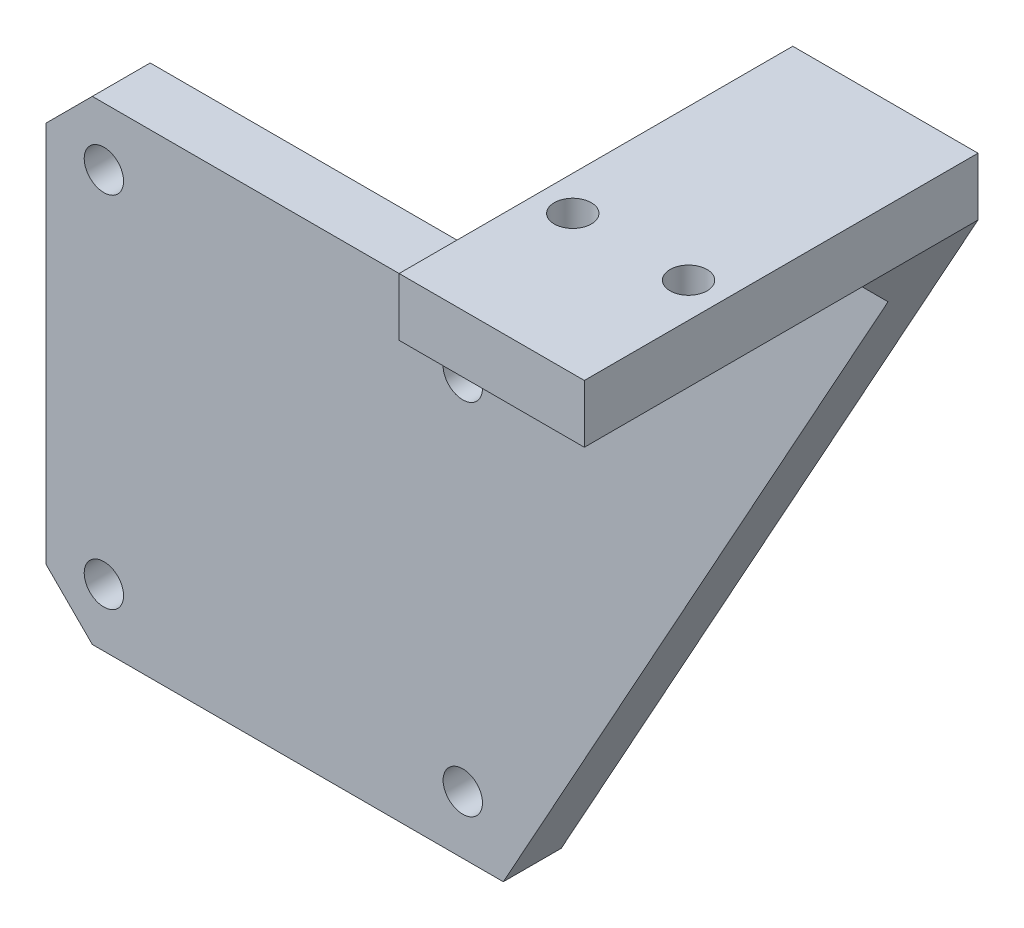
SolidWorks part; units mm, degrees
ref_plane "Přední rovina" through (0, 0, 0) normal (0, 0, 1) x (1, 0, 0)
ref_plane "Horní rovina" through (0, 0, 0) normal (0, 1, 0) x (1, 0, 0)
ref_plane "Pravá rovina" through (0, 0, 0) normal (1, 0, 0) x (0, 0, -1)
ref_plane "Rovina4" through (0, 0, 5) normal (0, 0, 1) x (1, 0, 0)
sketch "Skica1" plane through (0, 0, 5) normal (0, 0, 1) x (1, 0, 0)
  line L0 (46, 70) -> (-29.5, 70)
  line L1 (-29.5, 70) -> (-29.5, 0)
  line L2 (-29.5, 0) -> (10, 0)
  line L3 (10, 0) -> (46, 65)
  line L4 (46, 65) -> (46, 70)
extrude "Přidat vysunutím1" add sketch "Skica1" against normal blind 5
sketch "Skica2" plane through (0, 0, 5) normal (0, 0, 1) x (1, 0, 0)
  line L0 (25.8333, 60) -> (30, 65)
  line L1 (30, 65) -> (30, 70)
  line L2 (30, 70) -> (-29.5, 70)
  line L3 (-29.5, 70) -> (-29.5, 41)
  line L4 (-29.5, 41) -> (10, 41)
  line L5 (10, 41) -> (25.8333, 60)
extrude "Odebrat vysunutím1" cut sketch "Skica2" against normal through all
sketch "Skica3" plane through (0, 0, 5) normal (0, 0, 1) x (1, 0, 0)
  line L0 (30, 65) -> (30, 70)
  line L1 (30, 70) -> (46, 70)
  line L2 (46, 70) -> (46, 65)
  line L3 (46, 65) -> (30, 65)
extrude "Přidat vysunutím2" add sketch "Skica3" along normal blind 20
sketch "Skica5" plane through (0, 0, 5) normal (0, 0, 1) x (1, 0, 0)
  line L0 (-23.0975, 4.4681) -> (-23.0109, 4.8192)
  line L1 (-23.0109, 4.8192) -> (-23.0109, 5.1808)
  line L2 (-23.0109, 5.1808) -> (-23.0975, 5.5319)
  line L3 (-23.0975, 5.5319) -> (-23.2655, 5.8521)
  line L4 (-23.2655, 5.8521) -> (-23.5053, 6.1228)
  line L5 (-23.5053, 6.1228) -> (-23.8029, 6.3282)
  line L6 (-23.8029, 6.3282) -> (-24.141, 6.4564)
  line L7 (-24.141, 6.4564) -> (-24.5, 6.5)
  line L8 (-24.5, 6.5) -> (-24.859, 6.4564)
  line L9 (-24.859, 6.4564) -> (-25.1971, 6.3282)
  line L10 (-25.1971, 6.3282) -> (-25.4947, 6.1228)
  line L11 (-25.4947, 6.1228) -> (-25.7345, 5.8521)
  line L12 (-25.7345, 5.8521) -> (-25.9025, 5.5319)
  line L13 (-25.9025, 5.5319) -> (-25.9891, 5.1808)
  line L14 (-25.9891, 5.1808) -> (-25.9891, 4.8192)
  line L15 (-25.9891, 4.8192) -> (-25.9025, 4.4681)
  line L16 (-25.9025, 4.4681) -> (-25.7345, 4.1479)
  line L17 (-25.7345, 4.1479) -> (-25.4947, 3.8772)
  line L18 (-25.4947, 3.8772) -> (-25.1971, 3.6718)
  line L19 (-25.1971, 3.6718) -> (-24.859, 3.5436)
  line L20 (-24.859, 3.5436) -> (-24.5, 3.5)
  line L21 (-24.5, 3.5) -> (-24.141, 3.5436)
  line L22 (-24.141, 3.5436) -> (-23.8029, 3.6718)
  line L23 (-23.8029, 3.6718) -> (-23.5053, 3.8772)
  line L24 (-23.5053, 3.8772) -> (-23.2655, 4.1479)
  line L25 (-23.2655, 4.1479) -> (-23.0975, 4.4681)
extrude "Odebrat vysunutím3" cut sketch "Skica5" against normal through all
sketch "Skica6" plane through (0, 0, 5) normal (0, 0, 1) x (1, 0, 0)
  line L0 (5.5053, 3.8772) -> (5.8029, 3.6718)
  line L1 (5.8029, 3.6718) -> (6.141, 3.5436)
  line L2 (6.141, 3.5436) -> (6.5, 3.5)
  line L3 (6.5, 3.5) -> (6.859, 3.5436)
  line L4 (6.859, 3.5436) -> (7.1971, 3.6718)
  line L5 (7.1971, 3.6718) -> (7.4947, 3.8772)
  line L6 (7.4947, 3.8772) -> (7.7345, 4.1479)
  line L7 (7.7345, 4.1479) -> (7.9025, 4.4681)
  line L8 (7.9025, 4.4681) -> (7.9891, 4.8192)
  line L9 (7.9891, 4.8192) -> (7.9891, 5.1808)
  line L10 (7.9891, 5.1808) -> (7.9025, 5.5319)
  line L11 (7.9025, 5.5319) -> (7.7345, 5.8521)
  line L12 (7.7345, 5.8521) -> (7.4947, 6.1228)
  line L13 (7.4947, 6.1228) -> (7.1971, 6.3282)
  line L14 (7.1971, 6.3282) -> (6.859, 6.4564)
  line L15 (6.859, 6.4564) -> (6.5, 6.5)
  line L16 (6.5, 6.5) -> (6.141, 6.4564)
  line L17 (6.141, 6.4564) -> (5.8029, 6.3282)
  line L18 (5.8029, 6.3282) -> (5.5053, 6.1228)
  line L19 (5.5053, 6.1228) -> (5.2655, 5.8521)
  line L20 (5.2655, 5.8521) -> (5.0975, 5.5319)
  line L21 (5.0975, 5.5319) -> (5.0109, 5.1808)
  line L22 (5.0109, 5.1808) -> (5.0109, 4.8192)
  line L23 (5.0109, 4.8192) -> (5.0975, 4.4681)
  line L24 (5.0975, 4.4681) -> (5.2655, 4.1479)
  line L25 (5.2655, 4.1479) -> (5.5053, 3.8772)
extrude "Odebrat vysunutím4" cut sketch "Skica6" against normal through all
sketch "Skica7" plane through (0, 0, 5) normal (0, 0, 1) x (1, 0, 0)
  line L0 (-23.3772, 35.0053) -> (-23.1718, 35.3029)
  line L1 (-23.1718, 35.3029) -> (-23.0436, 35.641)
  line L2 (-23.0436, 35.641) -> (-23, 36)
  line L3 (-23, 36) -> (-23.0436, 36.359)
  line L4 (-23.0436, 36.359) -> (-23.1718, 36.6971)
  line L5 (-23.1718, 36.6971) -> (-23.3772, 36.9947)
  line L6 (-23.3772, 36.9947) -> (-23.6479, 37.2345)
  line L7 (-23.6479, 37.2345) -> (-23.9681, 37.4025)
  line L8 (-23.9681, 37.4025) -> (-24.3192, 37.4891)
  line L9 (-24.3192, 37.4891) -> (-24.6808, 37.4891)
  line L10 (-24.6808, 37.4891) -> (-25.0319, 37.4025)
  line L11 (-25.0319, 37.4025) -> (-25.3521, 37.2345)
  line L12 (-25.3521, 37.2345) -> (-25.6228, 36.9947)
  line L13 (-25.6228, 36.9947) -> (-25.8282, 36.6971)
  line L14 (-25.8282, 36.6971) -> (-25.9564, 36.359)
  line L15 (-25.9564, 36.359) -> (-26, 36)
  line L16 (-26, 36) -> (-25.9564, 35.641)
  line L17 (-25.9564, 35.641) -> (-25.8282, 35.3029)
  line L18 (-25.8282, 35.3029) -> (-25.6228, 35.0053)
  line L19 (-25.6228, 35.0053) -> (-25.3521, 34.7655)
  line L20 (-25.3521, 34.7655) -> (-25.0319, 34.5975)
  line L21 (-25.0319, 34.5975) -> (-24.6808, 34.5109)
  line L22 (-24.6808, 34.5109) -> (-24.3192, 34.5109)
  line L23 (-24.3192, 34.5109) -> (-23.9681, 34.5975)
  line L24 (-23.9681, 34.5975) -> (-23.6479, 34.7655)
  line L25 (-23.6479, 34.7655) -> (-23.3772, 35.0053)
extrude "Odebrat vysunutím5" cut sketch "Skica7" against normal through all
sketch "Skica8" plane through (0, 0, 5) normal (0, 0, 1) x (1, 0, 0)
  line L0 (5.9681, 34.5975) -> (6.3192, 34.5109)
  line L1 (6.3192, 34.5109) -> (6.6808, 34.5109)
  line L2 (6.6808, 34.5109) -> (7.0319, 34.5975)
  line L3 (7.0319, 34.5975) -> (7.3521, 34.7655)
  line L4 (7.3521, 34.7655) -> (7.6228, 35.0053)
  line L5 (7.6228, 35.0053) -> (7.8282, 35.3029)
  line L6 (7.8282, 35.3029) -> (7.9564, 35.641)
  line L7 (7.9564, 35.641) -> (8, 36)
  line L8 (8, 36) -> (7.9564, 36.359)
  line L9 (7.9564, 36.359) -> (7.8282, 36.6971)
  line L10 (7.8282, 36.6971) -> (7.6228, 36.9947)
  line L11 (7.6228, 36.9947) -> (7.3521, 37.2345)
  line L12 (7.3521, 37.2345) -> (7.0319, 37.4025)
  line L13 (7.0319, 37.4025) -> (6.6808, 37.4891)
  line L14 (6.6808, 37.4891) -> (6.3192, 37.4891)
  line L15 (6.3192, 37.4891) -> (5.9681, 37.4025)
  line L16 (5.9681, 37.4025) -> (5.6479, 37.2345)
  line L17 (5.6479, 37.2345) -> (5.3772, 36.9947)
  line L18 (5.3772, 36.9947) -> (5.1718, 36.6971)
  line L19 (5.1718, 36.6971) -> (5.0436, 36.359)
  line L20 (5.0436, 36.359) -> (5, 36)
  line L21 (5, 36) -> (5.0436, 35.641)
  line L22 (5.0436, 35.641) -> (5.1718, 35.3029)
  line L23 (5.1718, 35.3029) -> (5.3772, 35.0053)
  line L24 (5.3772, 35.0053) -> (5.6479, 34.7655)
  line L25 (5.6479, 34.7655) -> (5.9681, 34.5975)
extrude "Odebrat vysunutím6" cut sketch "Skica8" against normal through all
chamfer "Zkosení1" distance 4 angle 45 1 edges at (-29.5, 41, 2.5)
chamfer "Zkosení2" distance 5 angle 45 1 edges at (38, 65, 5) first distance on face at (6.5, 36, 5)
chamfer "Zkosení3" distance 4 angle 45 1 edges at (-29.5, 0, 2.5) first distance on face at (-29.5, 18.5, 2.5)
sketch "Skica10" plane through (0, 65, 0) normal (0, -1, 0) x (1, 0, 0)
  line L1 (30, 10) -> (46, 10) construction
  line L4 (30, 25) -> (30, 10) construction
  circle A0 centre (33, 22) radius 1.6
  circle A1 centre (43, 22) radius 1.6
  dimension "D1" = 10
  dimension "D2" = 12
  dimension "D3" = 3
  dimension "D4" = 12
sketch "Skica11" plane through (0, 0, 0) normal (0, 0, -1) x (-1, 0, 0)
  circle A2 centre (-6.5, 36) radius 1.7
  circle A5 centre (24.5, 36) radius 1.7
  circle A7 centre (-6.5, 5) radius 1.7
  circle A8 centre (24.5, 5) radius 1.7
extrude "Odebrat vysunutím9" cut sketch "Skica11" against normal blind 10
sketch "Skica12" plane through (0, 0, 25) normal (0, 0, 1) x (1, 0, 0)
  line L1 (30, 70) -> (46, 70)
  line L2 (30, 70) -> (30, 65)
  line L3 (30, 65) -> (46, 65)
  line L4 (46, 70) -> (46, 65)
extrude "Přidat vysunutím3" add sketch "Skica12" along normal blind 9
extrude "Odebrat vysunutím10" cut sketch "Skica10" against normal blind 9
